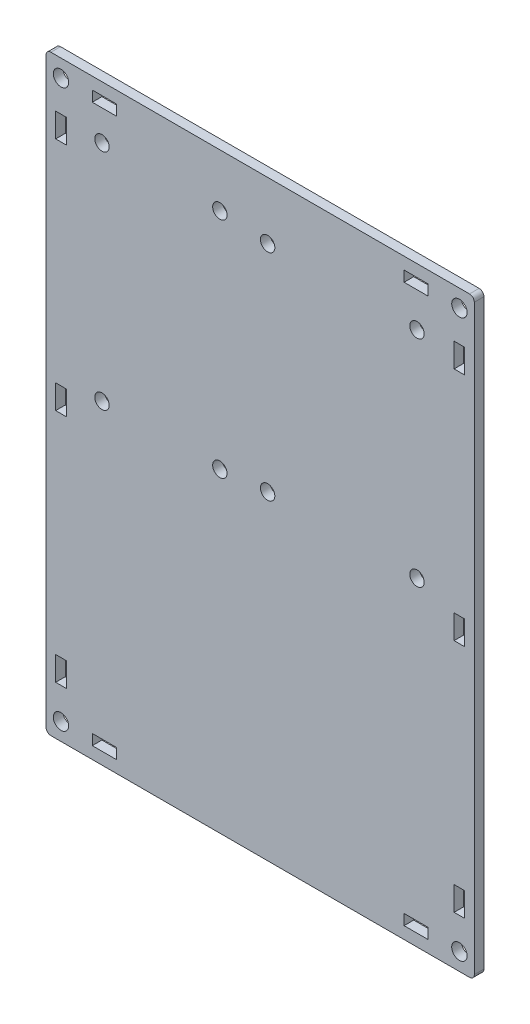
SolidWorks part; units mm, degrees
ref_plane "前基準面" through (0, 0, 0) normal (0, 0, 1) x (1, 0, 0)
ref_plane "上基準面" through (0, 0, 0) normal (0, 1, 0) x (1, 0, 0)
ref_plane "右基準面" through (0, 0, 0) normal (1, 0, 0) x (0, 0, -1)
sketch "Sketch1" plane through (0, 0, 0) normal (0, 0, 1) x (1, 0, 0)
  line L0 (-32.88, 50.5) -> (-44.5, 50.5) construction
  line L1 (-44.5, 61.5) -> (44.5, 61.5)
  line L2 (-44.5, 61.5) -> (-44.5, -61.5)
  line L3 (-44.5, -61.5) -> (44.5, -61.5)
  line L4 (44.5, 61.5) -> (44.5, -61.5)
  line L5 (-44.5, 61.5) -> (44.5, -61.5) construction
  line L6 (-44.5, -61.5) -> (44.5, 61.5) construction
  line L7 (-44.5, 50.5) -> (44.5, 50.5) construction
  line L8 (-32.88, 50.5) -> (-32.88, 61.5) construction
  line L9 (-32.88, 61.5) -> (-32.88, -61.5) construction
  line L10 (-8.38, 50.5) -> (-8.38, 61.5) construction
  line L11 (-8.38, 61.5) -> (-8.38, -61.5) construction
  line L12 (1.54, 49.58) -> (44.5, 49.58) construction
  line L13 (1.54, 49.58) -> (1.54, 61.5) construction
  line L14 (1.54, 61.5) -> (1.54, -61.5) construction
  line L15 (32.58, 49.58) -> (32.58, 61.5) construction
  line L16 (32.58, 61.5) -> (32.58, -61.5) construction
  line L17 (1.54, 4.88) -> (44.5, 4.88) construction
  line L18 (0, 0) -> (-45.154, 0) construction
  line L19 (-45.154, 0) -> (44.5, 0) construction
  line L20 (0, 0) -> (0, 61.5) construction
  line L21 (0, 61.5) -> (0, -61.5) construction
  line L22 (-41.4, 0) -> (-41.4, 61.5) construction
  line L23 (-40.3, 2.5) -> (-42.5, 2.5)
  line L24 (-40.3, 2.5) -> (-40.3, -2.5)
  line L25 (-40.3, -2.5) -> (-42.5, -2.5)
  line L26 (-42.5, 2.5) -> (-42.5, -2.5)
  line L27 (-40.3, 2.5) -> (-42.5, -2.5) construction
  line L28 (-40.3, -2.5) -> (-42.5, 2.5) construction
  line L29 (-41.4, 61.5) -> (-41.4, -61.5) construction
  line L30 (-42.5, -46.4) -> (-40.3, -46.4)
  line L31 (-42.5, 51.4) -> (-40.3, 51.4)
  line L32 (-42.5, 51.4) -> (-42.5, 46.4)
  line L33 (-42.5, 46.4) -> (-40.3, 46.4)
  line L34 (-40.3, 51.4) -> (-40.3, 46.4)
  line L35 (-42.5, 51.4) -> (-40.3, 46.4) construction
  line L36 (-42.5, 46.4) -> (-40.3, 51.4) construction
  line L37 (-40.3, -51.4) -> (-40.3, -46.4)
  line L38 (-42.5, -51.4) -> (-40.3, -51.4)
  line L39 (-42.5, -51.4) -> (-42.5, -46.4)
  line L40 (42.5, 46.4) -> (40.3, 46.4)
  line L41 (40.3, 51.4) -> (40.3, 46.4)
  line L42 (42.5, 51.4) -> (40.3, 51.4)
  line L43 (42.5, 51.4) -> (42.5, 46.4)
  line L44 (42.5, -51.4) -> (42.5, -46.4)
  line L45 (42.5, -51.4) -> (40.3, -51.4)
  line L46 (40.3, -51.4) -> (40.3, -46.4)
  line L47 (42.5, -46.4) -> (40.3, -46.4)
  line L48 (40.3, -2.5) -> (42.5, -2.5)
  line L49 (42.5, 2.5) -> (42.5, -2.5)
  line L50 (40.3, 2.5) -> (42.5, 2.5)
  line L51 (40.3, 2.5) -> (40.3, -2.5)
  line L52 (-41.4, 57.9) -> (41.4, 57.9) construction
  line L53 (34.9, 56.8) -> (29.9, 56.8)
  line L54 (-34.9, 59) -> (-29.9, 59)
  line L55 (-34.9, 59) -> (-34.9, 56.8)
  line L56 (-34.9, 56.8) -> (-29.9, 56.8)
  line L57 (-29.9, 59) -> (-29.9, 56.8)
  line L58 (-34.9, 59) -> (-29.9, 56.8) construction
  line L59 (-34.9, 56.8) -> (-29.9, 59) construction
  line L60 (29.9, 59) -> (29.9, 56.8)
  line L61 (34.9, 59) -> (29.9, 59)
  line L62 (34.9, 59) -> (34.9, 56.8)
  line L63 (34.9, -59) -> (34.9, -56.8)
  line L64 (34.9, -59) -> (29.9, -59)
  line L65 (29.9, -59) -> (29.9, -56.8)
  line L66 (34.9, -56.8) -> (29.9, -56.8)
  line L67 (-34.9, -56.8) -> (-29.9, -56.8)
  line L68 (-29.9, -59) -> (-29.9, -56.8)
  line L69 (-34.9, -59) -> (-29.9, -59)
  line L70 (-34.9, -59) -> (-34.9, -56.8)
  circle A0 centre (-32.88, 50.5) radius 1.5
  circle A2 centre (-8.38, 50.5) radius 1.5
  circle A3 centre (-32.88, 4) radius 1.5
  circle A4 centre (-8.38, 4) radius 1.5
  circle A5 centre (1.54, 49.58) radius 1.5
  circle A6 centre (32.58, 49.58) radius 1.5
  circle A7 centre (1.54, 4.88) radius 1.5
  circle A8 centre (32.58, 4.88) radius 1.5
  circle A9 centre (-41.4, 57.9) radius 1.6
  circle A10 centre (-41.4, -57.9) radius 1.6
  circle A11 centre (41.4, -57.9) radius 1.6
  circle A12 centre (41.4, 57.9) radius 1.6
  point P0 (0, 0)
  point P47 (-41.4, 0)
  point P54 (-41.4, 48.9)
  point P60 (-32.4, 57.9)
  dimension "D5" = 3
  dimension "D6" = 24.5
  dimension "D7" = 3
  dimension "D9" = 3
  dimension "D10" = 3
  dimension "D15" = 3
  dimension "D16" = 3
  dimension "D18" = 3
  dimension "D19" = 3
  dimension "D20" = 3.6
  dimension "D22" = 3.2
  dimension "D28" = 6.5
  dimension "D29" = 6.5
  dimension "D1" = 89
  dimension "123" = 123
  dimension "D3" = 11.62
  dimension "D4" = 11
  dimension "D8" = 46.5
  dimension "D11" = 46.5
  dimension "D12" = 9.92
  dimension "D13" = 11.92
  dimension "D14" = 31.04
  dimension "D17" = 44.7
  dimension "D21" = 5
  dimension "D23" = 2.2
  dimension "D24" = 2
  dimension "D25" = 5
  dimension "D26" = 2.2
  dimension "D27" = 5
  dimension "D30" = 2.2
extrude "Boss-Extrude1" add sketch "Sketch1" along normal blind 2
fillet "Fillet1" radius 1 4 edges at (44.5, -61.5, 1) (44.5, 61.5, 1) (-44.5, 61.5, 1) (-44.5, -61.5, 1)
